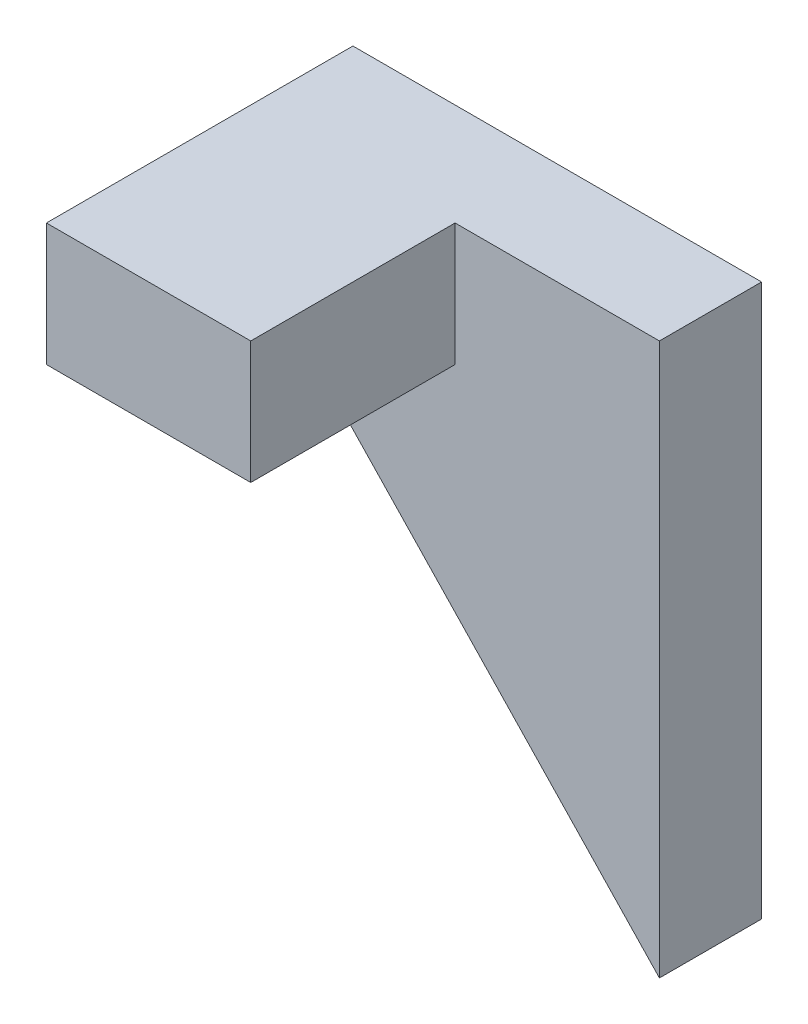
SolidWorks part; units mm, degrees
ref_plane "Front Plane" through (0, 0, 0) normal (0, 0, 1) x (1, 0, 0)
ref_plane "Top Plane" through (0, 0, 0) normal (0, 1, 0) x (1, 0, 0)
ref_plane "Right Plane" through (0, 0, 0) normal (1, 0, 0) x (0, 0, -1)
sketch "Sketch1" plane through (0, 0, 0) normal (0, 0, 1) x (1, 0, 0)
  line L0 (0, 0) -> (0, -12)
  line L1 (0, 0) -> (40, 0)
  line L2 (40, 0) -> (40, -54)
  line L3 (40, -54) -> (0, -12)
  line L4 (0, -12) -> (20, -12)
  line L5 (20, -12) -> (20, 0)
  dimension "D1" = 40
  dimension "D2" = 12
  dimension "D3" = 20
  dimension "D4" = 54
extrude "Boss-Extrude1" add sketch "Sketch1" along normal blind 10 contours L5 L4 L3 L2 L1 region at (27.4074, -21.5556, 0)
extrude "Boss-Extrude2" add sketch "Sketch1<4>" along normal blind 30 contours L4 L5 L1 L0 region at (10, -6, 0)
sketch "Sketch1<4>" plane through (0, 0, 0) normal (0, 0, 1) x (1, 0, 0) same geometry as "Sketch1"
